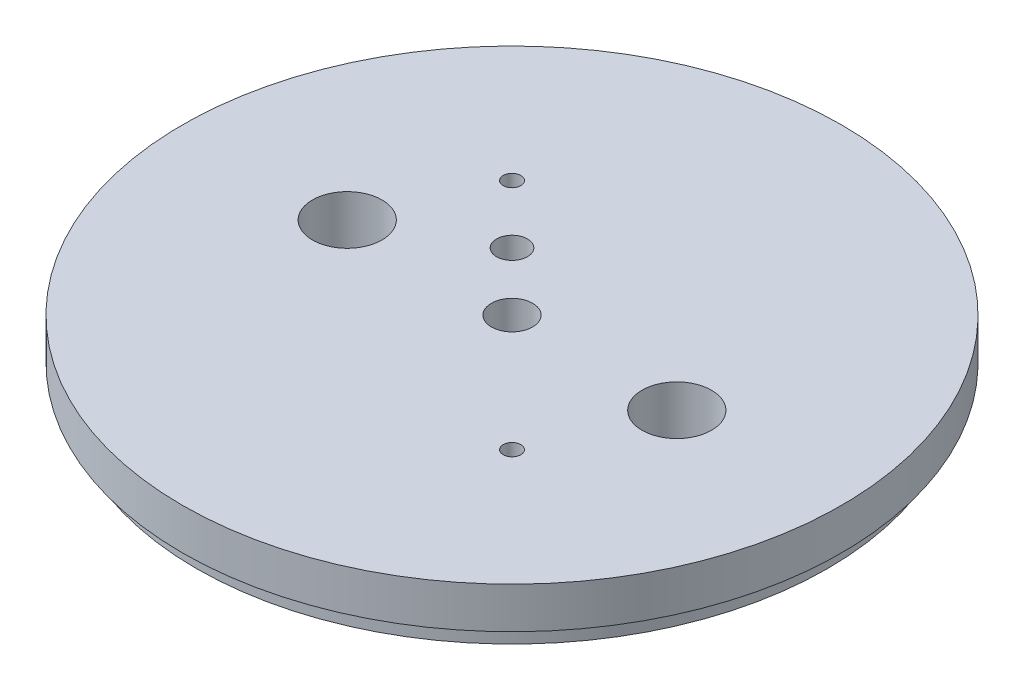
SolidWorks part; units mm, degrees
material "6061-T4 (SS)"
ref_plane "Front Plane" through (0, 0, 0) normal (0, 0, 1) x (1, 0, 0)
ref_plane "Top Plane" through (0, 0, 0) normal (0, 1, 0) x (1, 0, 0)
ref_plane "Right Plane" through (0, 0, 0) normal (1, 0, 0) x (0, 0, -1)
sketch "Sketch1" plane through (0, 0, 0) normal (0, 1, 0) x (1, 0, 0)
  line L0 (0, -50.8) -> (0, 50.8) construction
  line L1 (-50.8, 0) -> (50.8, 0) construction
  line L2 (-17.9605, 17.9605) -> (0, 0) construction
  line L3 (0, 56.7387) -> (0, 29.6936) construction
  line L4 (3.6407, 56.7387) -> (3.6407, 29.6936) construction
  line L5 (-3.6407, 56.7387) -> (-3.6407, 29.6936) construction
  line L6 (0, -56.7387) -> (0, -29.6936) construction
  line L7 (3.6407, -56.7387) -> (3.6407, -29.6936) construction
  line L8 (-3.6407, -56.7387) -> (-3.6407, -29.6936) construction
  line L9 (-35.921, -35.921) -> (54.3236, 54.3236) construction
  circle A0 centre (0, 0) radius 50.8
  circle A1 centre (0, 0) radius 3.175
  circle A2 centre (25.4, 0) radius 5.3578
  circle A3 centre (-25.4, 0) radius 5.3578
  circle A4 centre (-17.9605, 17.9605) radius 1.3589
  arc A6 (3.6407, 56.7387) -> (-3.6407, 56.7387) centre (0, 56.7387) ccw construction
  arc A7 (-3.6407, 29.6936) -> (3.6407, 29.6936) centre (0, 29.6936) ccw construction
  arc A8 (3.6407, -56.7387) -> (-3.6407, -56.7387) centre (0, -56.7387) cw construction
  arc A9 (-3.6407, -29.6936) -> (3.6407, -29.6936) centre (0, -29.6936) cw construction
  circle A10 centre (17.9605, -17.9605) radius 1.3589
  circle A11 centre (-8.9803, 8.9803) radius 2.3813
  circle A12 centre (8.9803, -8.9803) radius 2.3813 construction
  point P16 (0, 43.2162)
  point P19 (0, 0)
  point P26 (0, -43.2162)
  dimension "D1" = 101.6
  dimension "D2" = 6.35
  dimension "D3" = 10.7156
  dimension "D5" = 2.7178
  dimension "D8" = 4.7625
  dimension "D6" = 25.4
  dimension "D7" = 45
  dimension "D4" = 45
  dimension "D9" = 25.4
extrude "Boss-Extrude1" add sketch "Sketch1" along normal blind 9.525
sketch "Sketch2" plane through (0, 0, 0) normal (0, -1, 0) x (1, 0, 0)
  circle A0 centre (0, 0) radius 50.8
  circle A1 centre (0, 0) radius 48.641
  dimension "D1" = 101.6
  dimension "D2" = 97.282
extrude "Cut-Extrude1" cut sketch "Sketch2" against normal blind 3.175
sketch "Sketch3" plane through (0, 9.525, 0) normal (0, 1, 0) x (1, 0, 0)
  line L0 (0, 50.8) -> (0, -50.8) construction
  line L1 (-50.8, 0) -> (50.8, 0) construction
  line L2 (0, 34.798) -> (0, 13.97) construction
  line L3 (3.2385, 34.798) -> (3.2385, 13.97)
  line L4 (-3.2385, 34.798) -> (-3.2385, 13.97)
  line L5 (0, -34.798) -> (0, -13.97) construction
  line L6 (3.2385, -34.798) -> (3.2385, -13.97)
  line L7 (-3.2385, -34.798) -> (-3.2385, -13.97)
  circle A0 centre (0, 0) radius 50.8 construction
  arc A1 (3.2385, 34.798) -> (-3.2385, 34.798) centre (0, 34.798) ccw
  arc A2 (-3.2385, 13.97) -> (3.2385, 13.97) centre (0, 13.97) ccw
  arc A3 (3.2385, -34.798) -> (-3.2385, -34.798) centre (0, -34.798) cw
  arc A4 (-3.2385, -13.97) -> (3.2385, -13.97) centre (0, -13.97) cw
  point P7 (0, 13.97)
  point P8 (0, 34.798)
  point P12 (0, 24.384)
  point P20 (0, -24.384)
  point P25 (0, -34.798)
  point P26 (0, -13.97)
  dimension "D1" = 13.97
  dimension "D2" = 20.828
  dimension "D3" = 6.477
extrude "Cut-Extrude2" cut sketch "Sketch3" against normal blind 3.556 from offset 5.969 offset against normal yes
equation "\"Coupler_OD\" = 3.899in"
equation "\"Coupler_ID\" = 3.755in"
equation "\"Lead_Screw_Hole_Diam\" = (27/64)*1in"
equation "\"Lead_Screw_Dist\" = 2in"
equation "\"D9@Sketch1\"=\"Lead_Screw_Dist\"/2"
equation "\"D3@Sketch1\"=\"Lead_Screw_Hole_Diam\""
